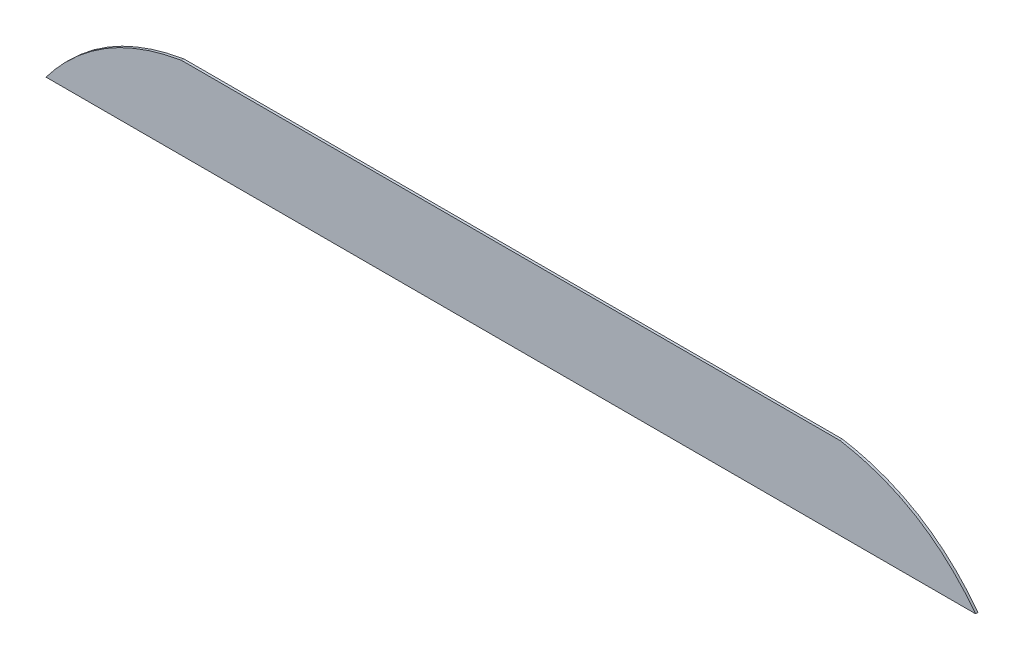
SolidWorks part; units mm, degrees
ref_plane "Front Plane" through (0, 0, 0) normal (0, 0, 1) x (1, 0, 0)
ref_plane "Top Plane" through (0, 0, 0) normal (0, 1, 0) x (1, 0, 0)
ref_plane "Right Plane" through (0, 0, 0) normal (1, 0, 0) x (0, 0, -1)
sketch "Sketch1" plane through (0, 0, 0) normal (0, 0, 1) x (1, 0, 0)
  line L0 (0, 0) -> (-304.8, 0)
  line L1 (0, 0) -> (609.6, 0)
  line L2 (0, 0) -> (0, 107.95) construction
  line L3 (0, 107.95) -> (609.6, 107.95)
  line L4 (609.6, 0) -> (609.6, 107.95) construction
  line L5 (609.6, 0) -> (914.4, 0)
  line L6 (304.8, -1000) -> (304.8, 49000) construction
  line L7 (0, 107.95) -> (-127, 107.95)
  line L8 (609.6, 107.95) -> (736.6, 107.95)
  spline S0 degree 2 poles (-304.8, 0) (-237.0558, 89.5085) (-127, 107.95) knots 0 0 0 1 1 1
  spline S1 degree 2 poles (914.4, 0) (846.6558, 89.5085) (736.6, 107.95) knots 0 0 0 1 1 1
  point P11 (304.8, 0)
  dimension "D1" = 609.6
  dimension "D2" = 107.95
  dimension "D3" = 304.8
  dimension "D4" = 127
extrude "Boss-Extrude1" add sketch "Sketch1" along normal blind 3.175
